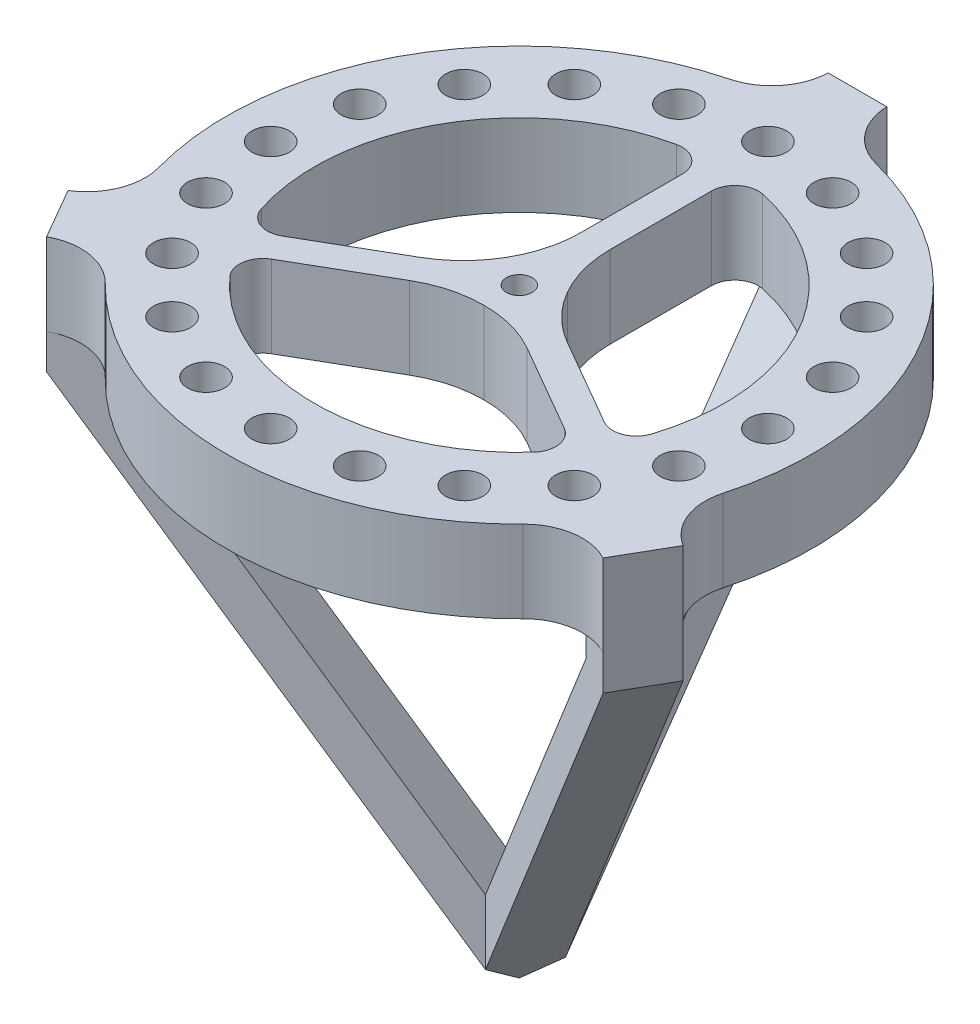
SolidWorks part; units mm, degrees
ref_plane "Front Plane" through (0, 0, 0) normal (0, 0, 1) x (1, 0, 0)
ref_plane "Top Plane" through (0, 0, 0) normal (0, 1, 0) x (1, 0, 0)
ref_plane "Right Plane" through (0, 0, 0) normal (1, 0, 0) x (0, 0, -1)
sketch "Sketch1" plane through (0, 0, 0) normal (0, 1, 0) x (1, 0, 0)
  circle A0 centre (0, 0) radius 1.1
  circle A1 centre (0, 0) radius 3
  dimension "D1" = 2.2
  dimension "D2" = 6
extrude "Boss-Extrude1" add sketch "Sketch1" along normal blind 5
sketch "Sketch4" plane through (0, 0, 0) normal (0, 1, 0) x (1, 0, 0)
  circle A0 centre (0, 0) radius 17.5
  circle A1 centre (0, 0) radius 25
  dimension "D1" = 50
  dimension "D2" = 35
extrude "Boss-Extrude2" add sketch "Sketch4" along normal blind 5 separate body
sketch "Sketch5" plane through (0, 5, 0) normal (0, 1, 0) x (1, 0, 0)
  line L1 (-1.25, 17.5) -> (1.25, 17.5)
  line L2 (-1.25, 17.5) -> (-1.25, 2.7272)
  line L3 (-1.25, 2.7272) -> (1.25, 2.7272)
  line L4 (1.25, 17.5) -> (1.25, 2.7272)
  line L5 (-1.25, 17.5) -> (1.25, 2.7272) construction
  line L6 (-1.25, 2.7272) -> (1.25, 17.5) construction
  circle A0 centre (0, 0) radius 3 construction
  circle A2 centre (0, 0) radius 17.5 construction
  point P0 (0, 10.1136)
  point P9 (0, 17.5)
  point P10 (0, 17.5)
  dimension "D1" = 2.5
extrude "Boss-Extrude3" add sketch "Sketch5" against normal up to surface (5 mm away) up to face at (0, 0, 25)
pattern_circular "CirPattern1" count 3 over 360 about axis through (0, 5, 0) along (0, -1, 0) of "Boss-Extrude3"
sketch "Sketch6" plane through (0, 5, 0) normal (0, 1, 0) x (1, 0, 0)
  line L0 (1.25, 17.4553) -> (-1.25, 17.4553) construction
  line L1 (-1.25, 17.4553) -> (0, 17.4553) construction
  line L2 (0, 17.4553) -> (0, 25) construction
  circle A0 centre (0, 21.2277) radius 1.59
  circle A1 centre (0, 0) radius 25 construction
  point P5 (0, 21.2277)
  dimension "D1" = 3.18
extrude "Cut-Extrude1" cut sketch "Sketch6" against normal blind 5
fillet "Fillet1" radius 10 6 edges at (-2.9868, 2.5, 0.2811) (-1.25, 2.5, -2.7272) (1.25, 2.5, -2.7272) (2.9868, 2.5, 0.2811) (1.7368, 2.5, 2.4461) (-1.7368, 2.5, 2.4461)
fillet "Fillet2" radius 2 6 edges at (15.7417, 2.5, 7.6451) (-14.4917, 2.5, 9.8102) (14.4917, 2.5, 9.8102) (-1.25, 2.5, -17.4553) (-15.7417, 2.5, 7.6451) (1.25, 2.5, -17.4553)
pattern_circular "CirPattern2" count 20 over 360 about axis through (0, 5, 0) along (0, -1, 0) of "Cut-Extrude1"
sketch "Sketch7" plane through (0, 0, 0) normal (0, -1, 0) x (1, 0, 0)
  line L0 (7.541, 23.2087) -> (4.4349, 22.5485)
  line L1 (0, 24.4031) -> (-2.75, 22.8154)
  line L2 (-2.75, 22.8154) -> (-2.75, 19.6399)
  line L3 (-2.75, 19.6399) -> (0, 18.0522)
  line L4 (0, 18.0522) -> (2.75, 19.6399)
  line L5 (2.75, 19.6399) -> (2.75, 22.8154)
  line L6 (2.75, 22.8154) -> (0, 24.4031)
  line L7 (4.4349, 22.5485) -> (3.4537, 19.5285)
  line L8 (3.4537, 19.5285) -> (5.5784, 17.1687)
  line L9 (5.5784, 17.1687) -> (8.6845, 17.8289)
  line L10 (8.6845, 17.8289) -> (9.6657, 20.8489)
  line L11 (9.6657, 20.8489) -> (7.541, 23.2087)
  line L12 (14.3438, 19.7425) -> (11.1857, 20.0744)
  line L13 (11.1857, 20.0744) -> (9.3193, 17.5055)
  line L14 (9.3193, 17.5055) -> (10.6108, 14.6046)
  line L15 (10.6108, 14.6046) -> (13.7689, 14.2726)
  line L16 (13.7689, 14.2726) -> (15.6353, 16.8416)
  line L17 (15.6353, 16.8416) -> (14.3438, 19.7425)
  line L18 (19.7425, 14.3438) -> (16.8416, 15.6353)
  line L19 (16.8416, 15.6353) -> (14.2726, 13.7689)
  line L20 (14.2726, 13.7689) -> (14.6046, 10.6108)
  line L21 (14.6046, 10.6108) -> (17.5055, 9.3193)
  line L22 (17.5055, 9.3193) -> (20.0744, 11.1857)
  line L23 (20.0744, 11.1857) -> (19.7425, 14.3438)
  line L24 (23.2087, 7.541) -> (20.8489, 9.6657)
  line L25 (20.8489, 9.6657) -> (17.8289, 8.6845)
  line L26 (17.8289, 8.6845) -> (17.1687, 5.5784)
  line L27 (17.1687, 5.5784) -> (19.5285, 3.4537)
  line L28 (19.5285, 3.4537) -> (22.5485, 4.4349)
  line L29 (22.5485, 4.4349) -> (23.2087, 7.541)
  line L30 (24.4031, 0) -> (22.8154, 2.75)
  line L31 (22.8154, 2.75) -> (19.6399, 2.75)
  line L32 (19.6399, 2.75) -> (18.0522, 0)
  line L33 (18.0522, 0) -> (19.6399, -2.75)
  line L34 (19.6399, -2.75) -> (22.8154, -2.75)
  line L35 (22.8154, -2.75) -> (24.4031, 0)
  line L36 (23.2087, -7.541) -> (22.5485, -4.4349)
  line L37 (22.5485, -4.4349) -> (19.5285, -3.4537)
  line L38 (19.5285, -3.4537) -> (17.1687, -5.5784)
  line L39 (17.1687, -5.5784) -> (17.8289, -8.6845)
  line L40 (17.8289, -8.6845) -> (20.8489, -9.6657)
  line L41 (20.8489, -9.6657) -> (23.2087, -7.541)
  line L42 (19.7425, -14.3438) -> (20.0744, -11.1857)
  line L43 (20.0744, -11.1857) -> (17.5055, -9.3193)
  line L44 (17.5055, -9.3193) -> (14.6046, -10.6108)
  line L45 (14.6046, -10.6108) -> (14.2726, -13.7689)
  line L46 (14.2726, -13.7689) -> (16.8416, -15.6353)
  line L47 (16.8416, -15.6353) -> (19.7425, -14.3438)
  line L48 (14.3438, -19.7425) -> (15.6353, -16.8416)
  line L49 (15.6353, -16.8416) -> (13.7689, -14.2726)
  line L50 (13.7689, -14.2726) -> (10.6108, -14.6046)
  line L51 (10.6108, -14.6046) -> (9.3193, -17.5055)
  line L52 (9.3193, -17.5055) -> (11.1857, -20.0744)
  line L53 (11.1857, -20.0744) -> (14.3438, -19.7425)
  line L54 (7.541, -23.2087) -> (9.6657, -20.8489)
  line L55 (9.6657, -20.8489) -> (8.6845, -17.8289)
  line L56 (8.6845, -17.8289) -> (5.5784, -17.1687)
  line L57 (5.5784, -17.1687) -> (3.4537, -19.5285)
  line L58 (3.4537, -19.5285) -> (4.4349, -22.5485)
  line L59 (4.4349, -22.5485) -> (7.541, -23.2087)
  line L60 (0, -24.4031) -> (2.75, -22.8154)
  line L61 (2.75, -22.8154) -> (2.75, -19.6399)
  line L62 (2.75, -19.6399) -> (0, -18.0522)
  line L63 (0, -18.0522) -> (-2.75, -19.6399)
  line L64 (-2.75, -19.6399) -> (-2.75, -22.8154)
  line L65 (-2.75, -22.8154) -> (0, -24.4031)
  line L66 (-7.541, -23.2087) -> (-4.4349, -22.5485)
  line L67 (-4.4349, -22.5485) -> (-3.4537, -19.5285)
  line L68 (-3.4537, -19.5285) -> (-5.5784, -17.1687)
  line L69 (-5.5784, -17.1687) -> (-8.6845, -17.8289)
  line L70 (-8.6845, -17.8289) -> (-9.6657, -20.8489)
  line L71 (-9.6657, -20.8489) -> (-7.541, -23.2087)
  line L72 (-14.3438, -19.7425) -> (-11.1857, -20.0744)
  line L73 (-11.1857, -20.0744) -> (-9.3193, -17.5055)
  line L74 (-9.3193, -17.5055) -> (-10.6108, -14.6046)
  line L75 (-10.6108, -14.6046) -> (-13.7689, -14.2726)
  line L76 (-13.7689, -14.2726) -> (-15.6353, -16.8416)
  line L77 (-15.6353, -16.8416) -> (-14.3438, -19.7425)
  line L78 (-19.7425, -14.3438) -> (-16.8416, -15.6353)
  line L79 (-16.8416, -15.6353) -> (-14.2726, -13.7689)
  line L80 (-14.2726, -13.7689) -> (-14.6046, -10.6108)
  line L81 (-14.6046, -10.6108) -> (-17.5055, -9.3193)
  line L82 (-17.5055, -9.3193) -> (-20.0744, -11.1857)
  line L83 (-20.0744, -11.1857) -> (-19.7425, -14.3438)
  line L84 (-23.2087, -7.541) -> (-20.8489, -9.6657)
  line L85 (-20.8489, -9.6657) -> (-17.8289, -8.6845)
  line L86 (-17.8289, -8.6845) -> (-17.1687, -5.5784)
  line L87 (-17.1687, -5.5784) -> (-19.5285, -3.4537)
  line L88 (-19.5285, -3.4537) -> (-22.5485, -4.4349)
  line L89 (-22.5485, -4.4349) -> (-23.2087, -7.541)
  line L90 (-24.4031, 0) -> (-22.8154, -2.75)
  line L91 (-22.8154, -2.75) -> (-19.6399, -2.75)
  line L92 (-19.6399, -2.75) -> (-18.0522, 0)
  line L93 (-18.0522, 0) -> (-19.6399, 2.75)
  line L94 (-19.6399, 2.75) -> (-22.8154, 2.75)
  line L95 (-22.8154, 2.75) -> (-24.4031, 0)
  line L96 (-23.2087, 7.541) -> (-22.5485, 4.4349)
  line L97 (-22.5485, 4.4349) -> (-19.5285, 3.4537)
  line L98 (-19.5285, 3.4537) -> (-17.1687, 5.5784)
  line L99 (-17.1687, 5.5784) -> (-17.8289, 8.6845)
  line L100 (-17.8289, 8.6845) -> (-20.8489, 9.6657)
  line L101 (-20.8489, 9.6657) -> (-23.2087, 7.541)
  line L102 (-19.7425, 14.3438) -> (-20.0744, 11.1857)
  line L103 (-20.0744, 11.1857) -> (-17.5055, 9.3193)
  line L104 (-17.5055, 9.3193) -> (-14.6046, 10.6108)
  line L105 (-14.6046, 10.6108) -> (-14.2726, 13.7689)
  line L106 (-14.2726, 13.7689) -> (-16.8416, 15.6353)
  line L107 (-16.8416, 15.6353) -> (-19.7425, 14.3438)
  line L108 (-14.3438, 19.7425) -> (-15.6353, 16.8416)
  line L109 (-15.6353, 16.8416) -> (-13.7689, 14.2726)
  line L110 (-13.7689, 14.2726) -> (-10.6108, 14.6046)
  line L111 (-10.6108, 14.6046) -> (-9.3193, 17.5055)
  line L112 (-9.3193, 17.5055) -> (-11.1857, 20.0744)
  line L113 (-11.1857, 20.0744) -> (-14.3438, 19.7425)
  line L114 (-7.541, 23.2087) -> (-9.6657, 20.8489)
  line L115 (-9.6657, 20.8489) -> (-8.6845, 17.8289)
  line L116 (-8.6845, 17.8289) -> (-5.5784, 17.1687)
  line L117 (-5.5784, 17.1687) -> (-3.4537, 19.5285)
  line L118 (-3.4537, 19.5285) -> (-4.4349, 22.5485)
  line L119 (-4.4349, 22.5485) -> (-7.541, 23.2087)
  circle A0 centre (0, 21.2277) radius 2.75 construction
  circle A2 centre (0, 0) radius 25
  circle A3 centre (0, 0) radius 25
  point P129 (0, 0)
  dimension "D1" = 5.5
  dimension "D2" = 0
  dimension "D3" = 20
extrude "Boss-Extrude4" add sketch "Sketch7" along normal blind 2
sketch "Sketch8" plane through (0, 0, 0) normal (0, 1, 0) x (1, 0, 0)
  line L12 (1.25, 15.1554) -> (1.25, 6.5144) construction
  line L13 (2.5962, 1.5033) -> (2.6, 1.4967) construction
  line L18 (6.2666, -2.1747) -> (13.75, -6.4952) construction
  line L21 (-2.6, 1.4967) -> (-2.5962, 1.5033) construction
  line L22 (-1.25, 6.5144) -> (-1.25, 15.1554) construction
  line L23 (-13.75, -6.4952) -> (-6.2666, -2.1747) construction
  line L24 (0.0038, -3) -> (-0.0038, -3) construction
  line L25 (-5.0166, -4.3397) -> (-12.5, -8.6603) construction
  line L26 (12.5, -8.6603) -> (5.0166, -4.3397) construction
  line L27 (1.25, 15.1554) -> (1.25, 6.5144)
  line L28 (2.5962, 1.5033) -> (2.6, 1.4967)
  line L29 (6.2666, -2.1747) -> (13.75, -6.4952)
  line L30 (-2.6, 1.4967) -> (-2.5962, 1.5033)
  line L31 (-1.25, 6.5144) -> (-1.25, 15.1554)
  line L32 (-13.75, -6.4952) -> (-6.2666, -2.1747)
  line L33 (0.0038, -3) -> (-0.0038, -3)
  line L34 (-5.0166, -4.3397) -> (-12.5, -8.6603)
  line L35 (12.5, -8.6603) -> (5.0166, -4.3397)
  arc A28 (1.25, 6.5144) -> (2.5962, 1.5033) centre (11.25, 6.5144) ccw construction
  circle A29 centre (0, 0) radius 1.1
  circle A30 centre (0, 0) radius 1.1
  arc A31 (2.6, 1.4967) -> (6.2666, -2.1747) centre (11.2666, 6.4856) ccw construction
  arc A32 (13.75, -6.4952) -> (16.6532, -5.3777) centre (14.75, -4.7631) ccw construction
  arc A33 (16.6532, -5.3777) -> (3.6694, 17.111) centre (0, 0) ccw construction
  arc A34 (3.6694, 17.111) -> (1.25, 15.1554) centre (3.25, 15.1554) ccw construction
  arc A45 (-2.5962, 1.5033) -> (-1.25, 6.5144) centre (-11.25, 6.5144) ccw construction
  arc A46 (-1.25, 15.1554) -> (-3.6694, 17.111) centre (-3.25, 15.1554) ccw construction
  arc A47 (-3.6694, 17.111) -> (-16.6532, -5.3777) centre (0, 0) ccw construction
  arc A48 (-16.6532, -5.3777) -> (-13.75, -6.4952) centre (-14.75, -4.7631) ccw construction
  arc A49 (-6.2666, -2.1747) -> (-2.6, 1.4967) centre (-11.2666, 6.4856) ccw construction
  arc A50 (-0.0038, -3) -> (-5.0166, -4.3397) centre (-0.0166, -13) ccw construction
  arc A51 (-12.5, -8.6603) -> (-12.9839, -11.7332) centre (-11.5, -10.3923) ccw construction
  arc A52 (-12.9839, -11.7332) -> (12.9839, -11.7332) centre (0, 0) ccw construction
  arc A53 (12.9839, -11.7332) -> (12.5, -8.6603) centre (11.5, -10.3923) ccw construction
  arc A54 (5.0166, -4.3397) -> (0.0038, -3) centre (0.0166, -13) ccw construction
  arc A55 (1.25, 6.5144) -> (2.5962, 1.5033) centre (11.25, 6.5144) ccw
  arc A56 (2.6, 1.4967) -> (6.2666, -2.1747) centre (11.2666, 6.4856) ccw
  arc A57 (13.75, -6.4952) -> (16.6532, -5.3777) centre (14.75, -4.7631) ccw
  arc A58 (16.6532, -5.3777) -> (3.6694, 17.111) centre (0, 0) ccw
  arc A59 (3.6694, 17.111) -> (1.25, 15.1554) centre (3.25, 15.1554) ccw
  arc A60 (-2.5962, 1.5033) -> (-1.25, 6.5144) centre (-11.25, 6.5144) ccw
  arc A61 (-1.25, 15.1554) -> (-3.6694, 17.111) centre (-3.25, 15.1554) ccw
  arc A62 (-3.6694, 17.111) -> (-16.6532, -5.3777) centre (0, 0) ccw
  arc A63 (-16.6532, -5.3777) -> (-13.75, -6.4952) centre (-14.75, -4.7631) ccw
  arc A64 (-6.2666, -2.1747) -> (-2.6, 1.4967) centre (-11.2666, 6.4856) ccw
  arc A65 (-0.0038, -3) -> (-5.0166, -4.3397) centre (-0.0166, -13) ccw
  arc A66 (-12.5, -8.6603) -> (-12.9839, -11.7332) centre (-11.5, -10.3923) ccw
  arc A67 (-12.9839, -11.7332) -> (12.9839, -11.7332) centre (0, 0) ccw
  arc A68 (12.9839, -11.7332) -> (12.5, -8.6603) centre (11.5, -10.3923) ccw
  arc A69 (5.0166, -4.3397) -> (0.0038, -3) centre (0.0166, -13) ccw
  dimension "D1" = 0
extrude "Cut-Extrude2" cut sketch "Sketch8" against normal blind 3
sketch "Sketch9" plane through (0, 5, 0) normal (0, 1, 0) x (1, 0, 0)
  line L0 (-2.5, 24.8747) -> (-2.5, 28.8747)
  line L2 (-2.5, 28.8747) -> (2.5, 28.8747)
  line L3 (2.5, 28.8747) -> (2.5, 24.8747)
  circle A1 centre (0, 0) radius 25 construction
  arc A2 (2.5, 24.8747) -> (-2.5, 24.8747) centre (0, 0) ccw
  point P9 (0, 25)
  dimension "D1" = 5
  dimension "D2" = 4
extrude "Boss-Extrude5" add sketch "Sketch9" against normal blind 10
sketch "Sketch10" plane through (0, 0, 0) normal (1, 0, 0) x (0, 0, -1)
  line L0 (28.8747, -5) -> (0, -46.2373)
  line L1 (0, -46.2373) -> (0, -40.7037)
  line L2 (0, -40.7037) -> (25, -5)
  line L3 (25, -5) -> (28.8747, -5)
  line L4 (-25, -2) -> (24.8747, -2) construction
  dimension "D1" = 55
extrude "Boss-Extrude6" add sketch "Sketch10" along normal mid plane 5
pattern_circular "CirPattern3" count 3 over 360 about axis through (0, 5, 0) along (0, -1, 0) of "Boss-Extrude5", "Boss-Extrude6"
fillet "Fillet3" radius 5 6 edges at (-22.7921, 1.5, 10.2723) (-20.2921, 1.5, 14.6024) (20.2921, 1.5, 14.6024) (22.7921, 1.5, 10.2723) (-2.5, 1.5, -24.8747) (2.5, 1.5, -24.8747)
sketch "Sketch15" plane through (0, -15.2116, -21.7244) normal (0, -0.5736, -0.8192) x (-1, 0, 0)
  line L7 (-2.5, -37.8754) -> (-2.5, -35.359)
  line L8 (-2.5, -35.359) -> (-1.25, -34.1007)
  line L9 (-1.25, -34.1007) -> (1.25, -34.1007)
  line L10 (1.25, -34.1007) -> (2.5, -35.359)
  line L11 (2.5, -35.359) -> (2.5, -37.8754)
  line L12 (2.5, -37.8754) -> (-2.5, -37.8754)
extrude "Cut-Extrude6" cut sketch "Sketch15" along normal blind 10
sketch "Sketch16" plane through (18.8139, -15.2116, 10.8622) normal (0.7094, -0.5736, 0.4096) x (0.3185, -0.2575, -0.9123)
  line L1 (11.9067, -35.9552) -> (9.5335, -36.7411)
  line L2 (9.5335, -36.7411) -> (8.7424, -34.3522)
  line L3 (8.7424, -34.3522) -> (9.5335, -32.7648)
  line L4 (9.5335, -32.7648) -> (11.9067, -31.9789)
  line L5 (11.9067, -31.9789) -> (13.4889, -32.7804)
  line L6 (11.9067, -35.9552) -> (13.5985, -34.3834)
  line L7 (13.5985, -34.3834) -> (13.4889, -32.7804)
  dimension "D1" = 1.6918
extrude "Cut-Extrude8" cut sketch "Sketch16" along normal blind 10
sketch "Sketch17" plane through (-18.8139, -15.2116, 10.8622) normal (-0.7094, -0.5736, 0.4096) x (0.3185, 0.2575, 0.9123)
  line L0 (-13.4889, -32.7804) -> (-11.9067, -31.9789)
  line L1 (-11.9067, -31.9789) -> (-9.5335, -32.7648)
  line L2 (-9.5335, -32.7648) -> (-8.7424, -34.3522)
  line L3 (-8.7424, -34.3522) -> (-8.1619, -35.5171)
  line L4 (-8.1619, -35.5171) -> (-11.8627, -37.3615)
  line L5 (-11.8627, -37.3615) -> (-13.758, -33.5585)
  line L6 (-13.758, -33.5585) -> (-13.4889, -32.7804)
  dimension "D1" = 4.135
  dimension "D2" = 0.7781
  dimension "D3" = 4.249
extrude "Cut-Extrude9" cut sketch "Sketch17" along normal blind 10
